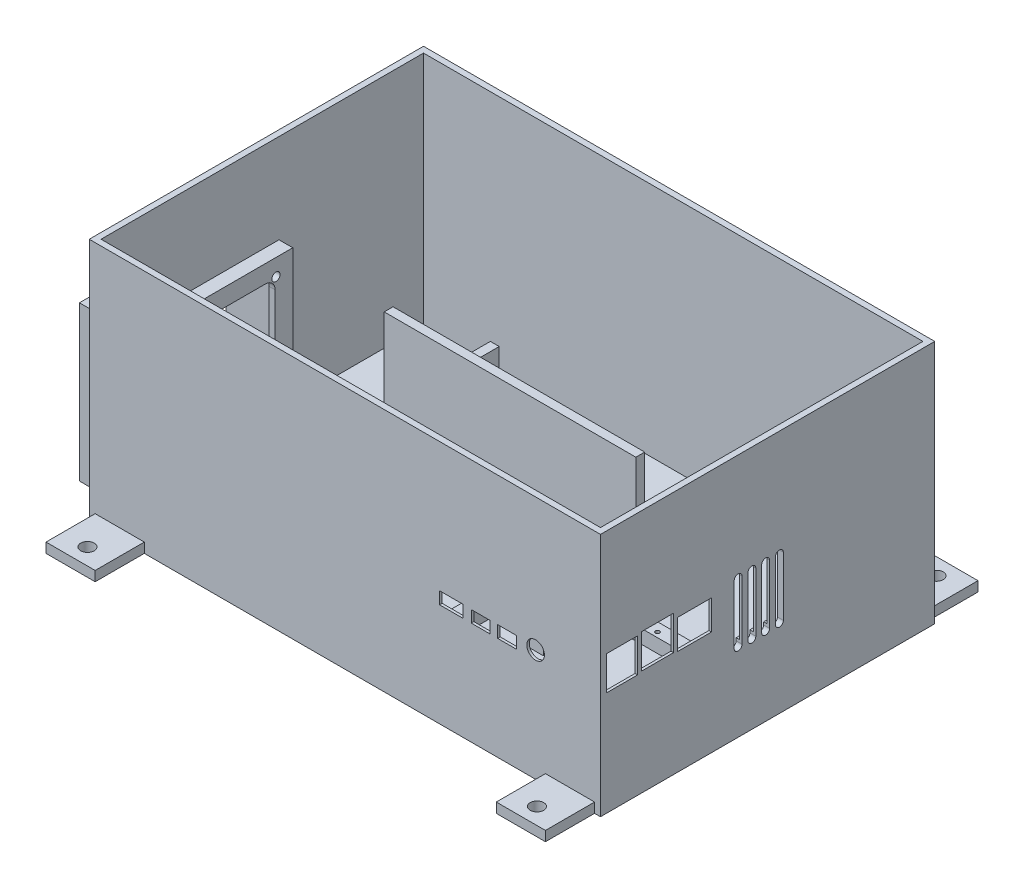
SolidWorks part; units mm, degrees
ref_plane "Front Plane" through (0, 0, 0) normal (0, 0, 1) x (1, 0, 0)
ref_plane "Top Plane" through (0, 0, 0) normal (0, 1, 0) x (1, 0, 0)
ref_plane "Right Plane" through (0, 0, 0) normal (1, 0, 0) x (0, 0, -1)
sketch "Sketch1" plane through (0, 0, 0) normal (0, 1, 0) x (1, 0, 0)
  line L1 (-130, -85) -> (130, -85)
  line L2 (-130, -85) -> (-130, 85)
  line L3 (-130, 85) -> (130, 85)
  line L4 (130, -85) -> (130, 85)
  line L5 (-130, -85) -> (130, 85) construction
  line L6 (-130, 85) -> (130, -85) construction
  point P0 (0, 0)
  dimension "D1" = 170
  dimension "D2" = 260
extrude "Floor" add sketch "Sketch1" along normal blind 4.3805
sketch "Sketch2" plane through (0, 4.3805, 0) normal (0, 1, 0) x (1, 0, 0)
  line L0 (127, -82) -> (127, 82)
  line L1 (127, 82) -> (-127, 82)
  line L2 (-127, 82) -> (-127, -82)
  line L3 (-127, -82) -> (127, -82)
  line L4 (130, -85) -> (130, 85)
  line L5 (130, 85) -> (-130, 85)
  line L6 (-130, 85) -> (-130, -85)
  line L7 (-130, -85) -> (130, -85)
  line L8 (130, -85) -> (130, 85)
  line L9 (130, 85) -> (-130, 85)
  line L10 (-130, 85) -> (-130, -85)
  line L11 (-130, -85) -> (130, -85)
  dimension "D1" = 0
  dimension "D2" = 3
extrude "Wall" add sketch "Sketch2" along normal blind 120
sketch "Sketch4" plane through (0, 4.3805, 0) normal (0, 1, 0) x (1, 0, 0)
  line L0 (120, -33) -> (49, -33)
  line L1 (127, -82) -> (42, -82)
  line L2 (127, -82) -> (127, -26)
  line L3 (127, -26) -> (42, -26)
  line L4 (42, -82) -> (42, -26)
  line L5 (49, -75) -> (49, -33)
  line L6 (120, -75) -> (49, -75)
  line L7 (120, -75) -> (120, -33)
  dimension "D1" = 85
  dimension "D2" = 56
  dimension "D3" = 7
extrude "Rpi stand" add sketch "Sketch4" along normal blind 7 from offset 30
sketch "Sketch7" plane through (0, 124.3805, 0) normal (0, 1, 0) x (1, 0, 0)
  point P11 (-127, -82)
  point P19 (-126.474, -85)
  point P20 (-130, 85)
sketch "Sketch3" plane through (0, 0, 0) normal (0, 1, 0) x (1, 0, 0)
  line L0 (-114.3, 101.6) -> (114.3, 101.6) construction
  line L1 (-127, 85) -> (-102, 85)
  line L2 (-127, 85) -> (-127, 110)
  line L3 (-127, 110) -> (-102, 110)
  line L4 (-102, 85) -> (-102, 110)
  line L5 (127, 85) -> (102, 85)
  line L6 (127, 85) -> (127, 110)
  line L7 (127, 110) -> (102, 110)
  line L8 (102, 85) -> (102, 110)
  line L9 (-127, -85) -> (-102, -85)
  line L10 (-127, -85) -> (-127, -110)
  line L11 (-127, -110) -> (-102, -110)
  line L12 (-102, -85) -> (-102, -110)
  line L13 (127, -85) -> (102, -85)
  line L14 (127, -85) -> (127, -110)
  line L15 (127, -110) -> (102, -110)
  line L16 (102, -85) -> (102, -110)
  line L17 (114.3, 101.6) -> (114.3, -101.6) construction
  line L18 (114.3, -101.6) -> (-114.3, -101.6) construction
  line L19 (-114.3, -101.6) -> (-114.3, 101.6) construction
  line L20 (-130, 0) -> (130, 0) construction
  line L21 (130, 85) -> (-130, 85) construction
  line L22 (130, -85) -> (130, 85) construction
  line L23 (0, 101.6) -> (0, -101.6) construction
  line L26 (-130, 85) -> (-130, -85) construction
  line L27 (-130, -85) -> (130, -85) construction
  circle A0 centre (-114.3, 101.6) radius 3.429
  circle A1 centre (114.3, 101.6) radius 3.429
  circle A2 centre (114.3, -101.6) radius 3.429
  circle A3 centre (-114.3, -101.6) radius 3.429
  point P4 (-130, -85)
  point P9 (130, -85)
  point P28 (-114.5, -85)
  point P29 (-102, -97.5)
  point P30 (114.5, -85)
  point P31 (-102, 97.5)
  dimension "D5" = 6.858
  dimension "D1" = 25
  dimension "D2" = 25
  dimension "D3" = 25
  dimension "D6" = 203.2
  dimension "D7" = 228.6
  dimension "D8" = 3
  dimension "D9" = 3
  dimension "D4" = 25
extrude "Brackets" add sketch "Sketch3" along normal blind 5
sketch "Sketch5" plane through (-130, 0, 0) normal (-1, 0, 0) x (0, 0, 1)
  line L0 (-8.5, 78.8805) -> (70, 78.8805)
  line L1 (-1, 4.3805) -> (62.5, 4.3805)
  line L2 (-4.5, 7.8805) -> (-4.5, 71.3805)
  line L3 (-1, 74.8805) -> (62.5, 74.8805)
  line L4 (66, 7.8805) -> (66, 71.3805)
  line L5 (70, 0.3805) -> (70, 78.8805)
  line L6 (-8.5, 0.3805) -> (70, 0.3805)
  line L7 (-8.5, 0.3805) -> (-8.5, 78.8805)
  line L8 (-4.5, 4.3805) -> (66, 4.3805) construction
  line L9 (110, 5) -> (110, 0) construction
  line L10 (-4.5, 4.3805) -> (-4.5, 74.8805) construction
  line L11 (-82, 4.3805) -> (82, 4.3805) construction
  line L12 (66, 4.3805) -> (66, 74.8805) construction
  line L13 (-4.5, 74.8805) -> (66, 74.8805) construction
  arc A0 (-1, 4.3805) -> (-4.5, 7.8805) centre (-1, 7.8805) cw
  arc A1 (62.5, 4.3805) -> (66, 7.8805) centre (62.5, 7.8805) ccw
  arc A2 (62.5, 74.8805) -> (66, 71.3805) centre (62.5, 71.3805) cw
  arc A3 (-4.5, 71.3805) -> (-1, 74.8805) centre (-1, 71.3805) cw
  dimension "D4" = 3.5
  dimension "D1" = 70.5
  dimension "D2" = 70.5
  dimension "D5" = 40
  dimension "D3" = 4
extrude "Fan Holder" add sketch "Sketch5" along normal blind 20 and the other way blind 10
sketch "Sketch8" plane through (-130, 0, 0) normal (-1, 0, 0) x (0, 0, 1)
  line L4 (-4.5, 71.3805) -> (-4.5, 7.8805)
  line L5 (-1, 4.3805) -> (62.5, 4.3805)
  line L6 (66, 7.8805) -> (66, 71.3805)
  line L7 (62.5, 74.8805) -> (-1, 74.8805)
  line L8 (-4.5, 71.3805) -> (-4.5, 7.8805)
  line L9 (-1, 4.3805) -> (62.5, 4.3805)
  line L10 (66, 7.8805) -> (66, 71.3805)
  line L23 (62.5, 74.8805) -> (-1, 74.8805)
  arc A2 (-4.5, 7.8805) -> (-1, 4.3805) centre (-1, 7.8805) ccw
  arc A3 (-4.5, 7.8805) -> (-1, 4.3805) centre (-1, 7.8805) ccw
  arc A4 (62.5, 4.3805) -> (66, 7.8805) centre (62.5, 7.8805) ccw
  arc A5 (62.5, 4.3805) -> (66, 7.8805) centre (62.5, 7.8805) ccw
  arc A8 (66, 71.3805) -> (62.5, 74.8805) centre (62.5, 71.3805) ccw
  arc A14 (66, 71.3805) -> (62.5, 74.8805) centre (62.5, 71.3805) ccw
  arc A16 (-1, 74.8805) -> (-4.5, 71.3805) centre (-1, 71.3805) ccw
  arc A17 (-1, 74.8805) -> (-4.5, 71.3805) centre (-1, 71.3805) ccw
  dimension "D1" = 0
extrude "Fan hole" cut sketch "Sketch8" against normal up to next
sketch "Sketch11" plane through (-120, 0, 0) normal (-1, 0, 0) x (0, 0, 1)
  line L0 (-8.5, 39.6305) -> (70, 39.6305) construction
  line L1 (30.75, 78.8805) -> (30.75, 0.3805) construction
  line L3 (0.05, 8.9305) -> (61.45, 8.9305) construction
  line L4 (-8.5, 78.8805) -> (-8.5, 0.3805)
  line L5 (-8.5, 0.3805) -> (70, 0.3805)
  line L6 (70, 0.3805) -> (70, 78.8805)
  line L7 (70, 78.8805) -> (-8.5, 78.8805)
  line L8 (-8.5, 78.8805) -> (-8.5, 0.3805)
  line L9 (-8.5, 0.3805) -> (70, 0.3805)
  line L10 (70, 0.3805) -> (70, 78.8805)
  line L11 (70, 78.8805) -> (-8.5, 78.8805)
  line L12 (0.05, 8.9305) -> (0.05, 70.3305) construction
  line L13 (0.05, 70.3305) -> (61.45, 70.3305) construction
  line L14 (61.45, 8.9305) -> (61.45, 70.3305) construction
  line L15 (0.05, 8.9305) -> (61.45, 70.3305) construction
  line L16 (0.5, 69.8805) -> (0.5, 9.3805)
  line L17 (0.5, 9.3805) -> (61, 9.3805)
  line L18 (61, 9.3805) -> (61, 69.8805)
  line L19 (61, 69.8805) -> (0.5, 69.8805)
  line L20 (0.5, 64.8805) -> (0.5, 14.3805)
  line L21 (5.5, 9.3805) -> (56, 9.3805)
  line L22 (61, 14.3805) -> (61, 64.8805)
  line L23 (56, 69.8805) -> (5.5, 69.8805)
  line L24 (0.05, 70.3305) -> (61.45, 8.9305) construction
  arc A0 (0.5, 14.3805) -> (5.5, 9.3805) centre (5.5, 14.3805) ccw
  arc A1 (56, 9.3805) -> (61, 14.3805) centre (56, 14.3805) ccw
  arc A2 (61, 64.8805) -> (56, 69.8805) centre (56, 64.8805) ccw
  arc A3 (0.5, 64.8805) -> (5.5, 69.8805) centre (5.5, 64.8805) cw
  circle A4 centre (0.05, 70.3305) radius 2.1
  circle A5 centre (61.45, 70.3305) radius 2.1
  circle A6 centre (61.45, 8.9305) radius 2.1
  circle A7 centre (0.05, 8.9305) radius 2.1
  point P24 (30.75, 39.6305)
  point P34 (30.75, 39.6305)
  dimension "D3" = 5
  dimension "D6" = 4.2
  dimension "D4" = 61.4
  dimension "D5" = 61.4
  dimension "D1" = 0
  dimension "D2" = 9
extrude "Boss-Extrude9" add sketch "Sketch11" along normal blind 3
sketch "Sketch12" plane through (0, 34.3805, 0) normal (0, -1, 0) x (1, 0, 0)
  line L1 (42, 26) -> (49, 26)
  line L2 (42, 26) -> (42, 33)
  line L3 (42, 33) -> (49, 33)
  line L4 (49, 26) -> (49, 33)
  dimension "D1" = 7
  dimension "D2" = 7
extrude "Boss-Extrude10" add sketch "Sketch12" along normal up to next
sketch "Sketch13" plane through (0, 4.3805, 0) normal (0, 1, 0) x (1, 0, 0)
  line L0 (127, 82) -> (-127, 82) construction
  line L2 (-107, -57) -> (-107, 5.7) construction
  line L3 (-107, 5.7) -> (-69.4, 5.7) construction
  line L4 (-107, -57) -> (-69.4, -57) construction
  line L5 (-69.4, 5.7) -> (-69.4, -57) construction
  line L6 (-69.4, 5.7) -> (-57.4, 5.7) construction
  line L7 (-57.4, 5.7) -> (-57.4, -57) construction
  line L8 (-57.4, -57) -> (-19.8, -57) construction
  line L9 (-19.8, -57) -> (-19.8, 5.7) construction
  line L10 (-19.8, 5.7) -> (-57.4, 5.7) construction
  line L11 (-69.4, -57) -> (-57.4, -57) construction
  line L12 (-19.8, -57) -> (62.83, -57) construction
  line L13 (62.83, -57) -> (62.83, -25.4) construction
  line L14 (62.83, -25.4) -> (105, -25.4) construction
  line L15 (105, -25.4) -> (105, -57) construction
  line L16 (105, -57) -> (62.83, -57) construction
  line L17 (118, 82) -> (118, 21.5) construction
  line L18 (-16.3, -57.85) -> (-16.3, 6.55) construction
  line L20 (127, -82) -> (127, 82) construction
  line L21 (118, 21.5) -> (120.7, 21.5) construction
  line L22 (118, 21.5) -> (41.5, 21.5) construction
  line L23 (-6.3, -47) -> (30.69, -47) construction
  line L24 (-6.3, -47) -> (-6.3, -6.4) construction
  line L25 (-6.3, -6.4) -> (30.69, -6.4) construction
  line L26 (30.69, -47) -> (30.69, -6.4) construction
  line L27 (-6.3, -47) -> (30.69, -6.4) construction
  line L28 (-6.3, -6.4) -> (30.69, -47) construction
  line L29 (130, -85) -> (130, 85) construction
  line L30 (-127, -82) -> (127, -82) construction
  line L457 (-127, 8.5) -> (-127, -70) construction
  line L458 (-127, -82) -> (127, -82) construction
  circle A0 centre (-107, -57) radius 1.25
  circle A1 centre (-107, 5.7) radius 1.25
  circle A2 centre (-69.4, 5.7) radius 1.25
  circle A3 centre (-69.4, -57) radius 1.25
  circle A4 centre (-57.4, 5.7) radius 1.25
  circle A5 centre (-57.4, -57) radius 1.25
  circle A6 centre (-19.8, -57) radius 1.25
  circle A7 centre (-19.8, 5.7) radius 1.25
  circle A12 centre (120.7, 21.5) radius 1.25
  circle A13 centre (41.5, 21.5) radius 1.25
  circle A14 centre (-107, 5.7) radius 2.75
  circle A15 centre (-107, -57) radius 2.75
  circle A16 centre (-69.4, 5.7) radius 2.75
  circle A17 centre (-57.4, 5.7) radius 2.75
  circle A18 centre (-69.4, -57) radius 2.75
  circle A19 centre (-57.4, -57) radius 2.75
  circle A20 centre (-19.8, -57) radius 2.75
  circle A21 centre (-19.8, 5.7) radius 2.75
  circle A22 centre (62.83, -57) radius 2.5
  circle A23 centre (62.83, -25.4) radius 2.5
  circle A24 centre (105, -25.4) radius 2.5
  circle A25 centre (105, -57) radius 2.5
  circle A26 centre (-6.3, -47) radius 1.25
  circle A28 centre (-6.3, -47) radius 2.75
  circle A30 centre (-69.4, 5.7) radius 1.65 construction
  circle A31 centre (104.2333, -41.2) radius 1.5 construction
  circle A32 centre (104.2333, -41.2) radius 1.5 construction
  circle A33 centre (63.5933, -41.2) radius 1.5 construction
  circle A34 centre (63.5933, -41.2) radius 1.5 construction
  circle A35 centre (104.2333, -41.2) radius 3
  circle A36 centre (63.5933, -41.2) radius 3
  circle A37 centre (-6.3, -6.4) radius 1.25
  circle A38 centre (30.69, -6.4) radius 1.25
  circle A39 centre (30.69, -47) radius 1.25
  circle A40 centre (-6.3, -6.4) radius 2.75
  circle A41 centre (30.69, -6.4) radius 2.75
  circle A42 centre (30.69, -47) radius 2.75
  circle A43 centre (30.69, -6.4) radius 1.5 construction
  circle A44 centre (30.69, -6.4) radius 1.5 construction
  point P2 (-127, -82)
  point P3 (127, -82)
  point P8 (12.195, -26.7)
  point P31 (127, 82)
  point P32 (-127, 82)
  point P90 (-123, -62.5)
  point P91 (-123, -66)
  point P92 (-130, -70)
  point P93 (-130, 8.5)
  point P94 (-127, 8.5)
  point P95 (-127, -70)
  point P96 (-127, 8.5)
  point P97 (-120, 8.5)
  point P98 (-120, -70)
  point P99 (-127, -70)
  point P100 (-120, 8.5)
  point P101 (-120, -70)
  point P102 (-130, -85)
  point P103 (-127, -85)
  point P104 (-102, -85)
  point P105 (102, -85)
  point P106 (127, -85)
  point P107 (130, -85)
  point P108 (-130, 85)
  point P109 (-130, -85)
  point P110 (130, 85)
  point P111 (127, 85)
  point P112 (102, 85)
  point P113 (-102, 85)
  point P114 (-127, 85)
  point P115 (-130, 85)
  point P116 (130, -85)
  point P117 (130, 85)
  point P118 (-130, 85)
  point P119 (-130, -85)
  point P120 (130, 85)
  point P121 (-130, 85)
  point P122 (130, -85)
  point P123 (130, 85)
  point P124 (-130, -85)
  point P125 (130, -85)
  point P126 (-127, 82)
  point P127 (-127, -82)
  point P128 (127, 82)
  point P129 (-127, 82)
  point P130 (127, -82)
  point P131 (127, 82)
  point P132 (-127, -82)
  point P133 (127, -82)
  point P134 (-127, 82)
  point P135 (-127, 8.5)
  point P136 (-127, -70)
  point P137 (-127, -82)
  point P138 (127, -82)
  point P139 (127, 82)
  point P140 (42, -82)
  point P141 (127, -82)
  point P142 (42, -26)
  point P143 (42, -82)
  point P144 (127, -26)
  point P145 (42, -26)
  point P146 (127, -82)
  point P147 (127, -26)
  point P148 (42, -82)
  point P149 (127, -82)
  point P150 (42, -33)
  point P151 (42, -82)
  point P152 (127, -26)
  point P153 (49, -26)
  point P154 (127, -82)
  point P155 (127, -26)
  point P156 (49, -75)
  point P157 (120, -75)
  point P158 (49, -33)
  point P159 (49, -75)
  point P160 (120, -33)
  point P161 (49, -33)
  point P162 (120, -75)
  point P163 (120, -33)
  point P164 (49, -75)
  point P165 (120, -75)
  point P166 (49, -33)
  point P167 (49, -75)
  point P168 (120, -33)
  point P169 (49, -33)
  point P170 (120, -75)
  point P171 (120, -33)
  point P172 (-102, 110)
  point P173 (-127, 110)
  point P174 (-102, 85)
  point P175 (-102, 110)
  point P176 (-127, 85)
  point P177 (-102, 85)
  point P178 (-127, 110)
  point P179 (-127, 85)
  point P180 (-102, 110)
  point P181 (-127, 110)
  point P182 (-102, 85)
  point P183 (-102, 110)
  point P184 (-127, 110)
  point P185 (-127, 85)
  point P186 (-114.3, 101.6)
  point P187 (-111.0208, 102.6025)
  point P188 (-114.3, 101.6)
  point P189 (-111.0208, 102.6025)
  point P190 (114.3, 101.6)
  point P191 (117.5792, 102.6025)
  point P192 (114.3, 101.6)
  point P193 (117.5792, 102.6025)
  point P194 (127, 85)
  point P195 (127, 110)
  point P196 (127, 110)
  point P197 (102, 110)
  point P198 (102, 110)
  point P199 (102, 85)
  point P200 (127, 85)
  point P201 (127, 110)
  point P202 (127, 110)
  point P203 (102, 110)
  point P204 (102, 110)
  point P205 (102, 85)
  point P206 (102, 85)
  point P207 (127, 85)
  point P208 (-114.3, -101.6)
  point P209 (-111.0208, -100.5975)
  point P210 (-114.3, -101.6)
  point P211 (-111.0208, -100.5975)
  point P212 (-127, -85)
  point P213 (-127, -110)
  point P214 (-127, -110)
  point P215 (-102, -110)
  point P216 (-102, -110)
  point P217 (-102, -85)
  point P218 (-127, -85)
  point P219 (-127, -110)
  point P220 (-127, -110)
  point P221 (-102, -110)
  point P222 (-102, -110)
  point P223 (-102, -85)
  point P224 (-102, -85)
  point P225 (-127, -85)
  point P226 (114.3, -101.6)
  point P227 (117.5792, -100.5975)
  point P228 (114.3, -101.6)
  point P229 (117.5792, -100.5975)
  point P230 (127, -110)
  point P231 (127, -85)
  point P232 (102, -85)
  point P233 (102, -110)
  point P234 (102, -110)
  point P235 (127, -110)
  point P236 (127, -110)
  point P237 (127, -85)
  point P238 (127, -85)
  point P239 (102, -85)
  point P240 (102, -85)
  point P241 (102, -110)
  point P242 (102, -110)
  point P243 (127, -110)
  point P244 (-130, 8.5)
  point P245 (-130, -70)
  point P246 (-120, 8.5)
  point P247 (-127, 8.5)
  point P248 (-130, 8.5)
  point P249 (-150, 8.5)
  point P250 (-120, -70)
  point P251 (-127, -70)
  point P252 (-130, -70)
  point P253 (-150, -70)
  point P254 (-130, -70)
  point P255 (-150, -70)
  point P256 (-130, 8.5)
  point P257 (-150, 8.5)
  point P258 (-120, -70)
  point P259 (-120, 8.5)
  point P260 (-123, 4.5)
  point P261 (-150, 4.5)
  point P262 (-123, 4.5)
  point P263 (-150, 4.5)
  point P264 (-123, 1)
  point P265 (-150, 1)
  point P266 (-123, -62.5)
  point P267 (-150, -62.5)
  point P268 (-123, -66)
  point P269 (-150, -66)
  point P270 (-123, -66)
  point P271 (-150, -66)
  point P272 (-123, -62.5)
  point P273 (-150, -62.5)
  point P274 (-123, 1)
  point P275 (-150, 1)
  point P276 (-150, -70)
  point P277 (-150, 8.5)
  point P278 (-150, 8.5)
  point P279 (-150, -70)
  point P280 (-150, 4.5)
  point P281 (-150, 1)
  point P282 (-150, -62.5)
  point P283 (-150, 1)
  point P284 (-150, -62.5)
  point P285 (-150, -66)
  point P286 (-150, -62.5)
  point P287 (-150, -66)
  point P288 (-150, 1)
  point P289 (-150, -62.5)
  point P290 (-150, 4.5)
  point P291 (-150, 1)
  point P292 (-123, 4.5)
  point P293 (-123, 1)
  point P294 (-123, -62.5)
  point P295 (-123, 1)
  point P296 (-123, 4.5)
  point P297 (-123, 1)
  point P298 (-123, 1)
  point P299 (-123, -62.5)
  point P300 (-123, -62.5)
  point P301 (-123, -66)
  point P302 (-123, -5.5)
  point P303 (-120, -5.5)
  point P304 (-123, -56)
  point P305 (-120, -56)
  point P306 (-123, -61)
  point P307 (-120, -61)
  point P308 (-123, -61)
  point P309 (-120, -61)
  point P310 (-123, -56)
  point P311 (-120, -56)
  point P312 (-123, -5.5)
  point P313 (-120, -5.5)
  point P314 (-123, -0.5)
  point P315 (-120, -0.5)
  point P316 (-123, -0.5)
  point P317 (-120, -0.5)
  point P318 (-123, -0.5)
  point P319 (-123, -5.5)
  point P320 (-123, -56)
  point P321 (-123, -5.5)
  point P322 (-123, -56)
  point P323 (-123, -61)
  point P324 (-123, -56)
  point P325 (-123, -61)
  point P326 (-123, -5.5)
  point P327 (-123, -56)
  point P328 (-123, -0.5)
  point P329 (-123, -5.5)
  point P330 (-120, -5.5)
  point P331 (-120, -0.5)
  point P332 (-120, -56)
  point P333 (-120, -5.5)
  point P334 (-120, -61)
  point P335 (-120, -56)
  point P336 (-120, -61)
  point P337 (-120, -56)
  point P338 (-120, -5.5)
  point P339 (-120, -56)
  point P340 (-120, -5.5)
  point P341 (-120, -0.5)
  point P342 (-123, 2.05)
  point P343 (-123, -2.15)
  point P344 (-120, -2.15)
  point P345 (-120, 2.05)
  point P346 (-123, -59.35)
  point P347 (-123, -63.55)
  point P348 (-120, -63.55)
  point P349 (-120, -59.35)
  point P350 (-123, -59.35)
  point P351 (-123, -63.55)
  point P352 (-120, -63.55)
  point P353 (-120, -59.35)
  point P354 (-123, 2.05)
  point P355 (-123, -2.15)
  point P356 (-120, -2.15)
  point P357 (-120, 2.05)
  point P358 (49, -33)
  point P359 (42, -33)
  point P360 (49, -26)
  point P361 (49, -33)
  point P362 (42, -33)
  point P363 (42, -26)
  point P364 (42, -26)
  point P365 (49, -26)
  point P366 (49, -26)
  point P367 (49, -33)
  point P368 (49, -33)
  point P369 (42, -33)
  point P370 (-130, -85)
  point P371 (130, -85)
  point P372 (-130, -85)
  point P373 (-130, 85)
  point P374 (-130, 85)
  point P375 (130, 85)
  point P376 (130, -85)
  point P377 (130, 85)
  point P378 (-130, -85)
  point P379 (130, 85)
  point P380 (-130, 85)
  point P381 (130, -85)
  point P382 (127, -82)
  point P383 (127, 82)
  point P384 (127, 82)
  point P385 (-127, 82)
  point P386 (-127, 82)
  point P387 (-127, -82)
  point P388 (-127, -82)
  point P389 (127, -82)
  point P390 (130, -85)
  point P391 (130, 85)
  point P392 (130, 85)
  point P393 (-130, 85)
  point P394 (-130, 85)
  point P395 (-130, -85)
  point P396 (-130, -85)
  point P397 (130, -85)
  point P398 (130, -85)
  point P399 (130, 85)
  point P400 (130, 85)
  point P401 (-130, 85)
  point P402 (-130, 85)
  point P403 (-130, -85)
  point P404 (-130, -85)
  point P405 (130, -85)
  point P406 (120, -33)
  point P407 (49, -33)
  point P408 (127, -82)
  point P409 (42, -82)
  point P410 (127, -82)
  point P411 (127, -26)
  point P412 (127, -26)
  point P413 (42, -26)
  point P414 (42, -82)
  point P415 (42, -26)
  point P416 (49, -75)
  point P417 (49, -33)
  point P418 (120, -75)
  point P419 (49, -75)
  point P420 (120, -75)
  point P421 (120, -33)
  point P422 (-114.3, 101.6)
  point P423 (114.3, 101.6)
  point P424 (-127, 85)
  point P425 (-102, 85)
  point P426 (-127, 85)
  point P427 (-127, 110)
  point P428 (-127, 110)
  point P429 (-102, 110)
  point P430 (-102, 85)
  point P431 (-102, 110)
  point P432 (127, 85)
  point P433 (102, 85)
  point P434 (127, 85)
  point P435 (127, 110)
  point P436 (127, 110)
  point P437 (102, 110)
  point P438 (102, 85)
  point P439 (102, 110)
  point P440 (-127, -85)
  point P441 (-102, -85)
  point P442 (-127, -85)
  point P443 (-127, -110)
  point P444 (-127, -110)
  point P445 (-102, -110)
  point P446 (-102, -85)
  point P447 (-102, -110)
  point P448 (127, -85)
  point P449 (102, -85)
  point P450 (127, -85)
  point P451 (127, -110)
  point P452 (127, -110)
  point P453 (102, -110)
  point P454 (102, -85)
  point P455 (102, -110)
  point P456 (114.3, 101.6)
  point P457 (114.3, -101.6)
  point P458 (114.3, -101.6)
  point P459 (-114.3, -101.6)
  point P460 (-114.3, -101.6)
  point P461 (-114.3, 101.6)
  point P462 (-130, 0)
  point P463 (130, 0)
  point P464 (130, 85)
  point P465 (-130, 85)
  point P466 (130, -85)
  point P467 (130, 85)
  point P468 (0, 101.6)
  point P469 (0, -101.6)
  point P470 (-130, 85)
  point P471 (-130, -85)
  point P472 (-130, -85)
  point P473 (130, -85)
  point P474 (-130, 8.5)
  point P475 (-130, -70)
  point P476 (-130, 1)
  point P477 (-130, -62.5)
  point P478 (-130, 1)
  point P479 (-130, -62.5)
  point P480 (-130, 8.5)
  point P481 (-130, -70)
  point P482 (-130, 4.5)
  point P483 (-130, -66)
  point P484 (-130, 82)
  point P485 (-130, -82)
  point P486 (-130, 4.5)
  point P487 (-130, -66)
  point P488 (-130, 1)
  point P489 (-130, -62.5)
  point P490 (-130, -62.5)
  point P491 (-130, 1)
  point P492 (-130, 1)
  point P493 (-130, -62.5)
  point P494 (-130, -62.5)
  point P495 (-130, 1)
  point P496 (-120, 8.5)
  point P497 (-120, -70)
  point P498 (-120, -0.05)
  point P499 (-120, -61.45)
  point P500 (-120, 8.5)
  point P501 (-120, -70)
  point P502 (-120, -70)
  point P503 (-120, 8.5)
  point P504 (-120, 8.5)
  point P505 (-120, -70)
  point P506 (-120, -70)
  point P507 (-120, 8.5)
  point P508 (-120, -0.05)
  point P509 (-120, -61.45)
  point P510 (-120, -0.05)
  point P511 (-120, -61.45)
  point P512 (-120, -0.5)
  point P513 (-120, -61)
  point P514 (-120, -61)
  point P515 (-120, -0.5)
  point P516 (-120, -5.5)
  point P517 (-120, -56)
  point P518 (-120, -56)
  point P519 (-120, -5.5)
  point P520 (-120, -0.05)
  point P521 (-120, -61.45)
  point P522 (42, -26)
  point P523 (49, -26)
  point P524 (42, -26)
  point P525 (42, -33)
  point P526 (42, -33)
  point P527 (49, -33)
  point P528 (49, -26)
  point P529 (49, -33)
  point P530 (-123, -62.5)
  point P531 (-123, -66)
  point P532 (-130, -70)
  point P533 (-130, 8.5)
  point P534 (-127, 8.5)
  point P535 (-127, -70)
  point P536 (-127, 8.5)
  point P537 (-120, 8.5)
  point P538 (-120, -70)
  point P539 (-127, -70)
  point P540 (-120, 8.5)
  point P541 (-120, -70)
  point P542 (-130, -85)
  point P543 (-127, -85)
  point P544 (-102, -85)
  point P545 (102, -85)
  point P546 (127, -85)
  point P547 (130, -85)
  point P548 (-130, 85)
  point P549 (-130, -85)
  point P550 (130, 85)
  point P551 (127, 85)
  point P552 (102, 85)
  point P553 (-102, 85)
  point P554 (-127, 85)
  point P555 (-130, 85)
  point P556 (130, -85)
  point P557 (130, 85)
  point P558 (-130, 85)
  point P559 (-130, -85)
  point P560 (130, 85)
  point P561 (-130, 85)
  point P562 (130, -85)
  point P563 (130, 85)
  point P564 (-130, -85)
  point P565 (130, -85)
  point P566 (-127, 82)
  point P567 (-127, -82)
  point P568 (127, 82)
  point P569 (-127, 82)
  point P570 (127, -82)
  point P571 (127, 82)
  point P572 (-127, -82)
  point P573 (127, -82)
  point P574 (-127, 82)
  point P575 (-127, 8.5)
  point P576 (-127, -70)
  point P577 (-127, -82)
  point P578 (127, 82)
  point P579 (-127, 82)
  point P580 (127, -82)
  point P581 (127, 82)
  point P582 (-127, -82)
  point P583 (127, -82)
  point P584 (42, -82)
  point P585 (127, -82)
  point P586 (42, -26)
  point P587 (42, -82)
  point P588 (127, -26)
  point P589 (42, -26)
  point P590 (127, -82)
  point P591 (127, -26)
  point P592 (42, -82)
  point P593 (127, -82)
  point P594 (42, -33)
  point P595 (42, -82)
  point P596 (127, -26)
  point P597 (49, -26)
  point P598 (127, -82)
  point P599 (127, -26)
  point P600 (49, -75)
  point P601 (120, -75)
  point P602 (49, -33)
  point P603 (49, -75)
  point P604 (120, -33)
  point P605 (49, -33)
  point P606 (120, -75)
  point P607 (120, -33)
  point P608 (49, -75)
  point P609 (120, -75)
  point P610 (49, -33)
  point P611 (49, -75)
  point P612 (120, -33)
  point P613 (49, -33)
  point P614 (120, -75)
  point P615 (120, -33)
  point P616 (-102, 110)
  point P617 (-127, 110)
  point P618 (-102, 85)
  point P619 (-102, 110)
  point P620 (-127, 85)
  point P621 (-102, 85)
  point P622 (-127, 110)
  point P623 (-127, 85)
  point P624 (-102, 110)
  point P625 (-127, 110)
  point P626 (-102, 85)
  point P627 (-102, 110)
  point P628 (-127, 110)
  point P629 (-127, 85)
  point P630 (-114.3, 101.6)
  point P631 (-111.0208, 102.6025)
  point P632 (-114.3, 101.6)
  point P633 (-111.0208, 102.6025)
  point P634 (114.3, 101.6)
  point P635 (117.5792, 102.6025)
  point P636 (114.3, 101.6)
  point P637 (117.5792, 102.6025)
  point P638 (127, 85)
  point P639 (127, 110)
  point P640 (127, 110)
  point P641 (102, 110)
  point P642 (102, 110)
  point P643 (102, 85)
  point P644 (127, 85)
  point P645 (127, 110)
  point P646 (127, 110)
  point P647 (102, 110)
  point P648 (102, 110)
  point P649 (102, 85)
  point P650 (102, 85)
  point P651 (127, 85)
  point P652 (-114.3, -101.6)
  point P653 (-111.0208, -100.5975)
  point P654 (-114.3, -101.6)
  point P655 (-111.0208, -100.5975)
  point P656 (-127, -85)
  point P657 (-127, -110)
  point P658 (-127, -110)
  point P659 (-102, -110)
  point P660 (-102, -110)
  point P661 (-102, -85)
  point P662 (-127, -85)
  point P663 (-127, -110)
  point P664 (-127, -110)
  point P665 (-102, -110)
  point P666 (-102, -110)
  point P667 (-102, -85)
  point P668 (-102, -85)
  point P669 (-127, -85)
  point P670 (114.3, -101.6)
  point P671 (117.5792, -100.5975)
  point P672 (114.3, -101.6)
  point P673 (117.5792, -100.5975)
  point P674 (127, -110)
  point P675 (127, -85)
  point P676 (102, -85)
  point P677 (102, -110)
  point P678 (102, -110)
  point P679 (127, -110)
  point P680 (127, -110)
  point P681 (127, -85)
  point P682 (127, -85)
  point P683 (102, -85)
  point P684 (102, -85)
  point P685 (102, -110)
  point P686 (102, -110)
  point P687 (127, -110)
  point P688 (-130, 8.5)
  point P689 (-130, -70)
  point P690 (-120, 8.5)
  point P691 (-127, 8.5)
  point P692 (-130, 8.5)
  point P693 (-150, 8.5)
  point P694 (-120, -70)
  point P695 (-127, -70)
  point P696 (-130, -70)
  point P697 (-150, -70)
  point P698 (-130, -70)
  point P699 (-150, -70)
  point P700 (-130, 8.5)
  point P701 (-150, 8.5)
  point P702 (-120, -70)
  point P703 (-120, 8.5)
  point P704 (-123, 4.5)
  point P705 (-150, 4.5)
  point P706 (-123, 4.5)
  point P707 (-150, 4.5)
  point P708 (-123, 1)
  point P709 (-150, 1)
  point P710 (-123, -62.5)
  point P711 (-150, -62.5)
  point P712 (-123, -66)
  point P713 (-150, -66)
  point P714 (-123, -66)
  point P715 (-150, -66)
  point P716 (-123, -62.5)
  point P717 (-150, -62.5)
  point P718 (-123, 1)
  point P719 (-150, 1)
  point P720 (-150, -70)
  point P721 (-150, 8.5)
  point P722 (-150, 8.5)
  point P723 (-150, -70)
  point P724 (-150, 4.5)
  point P725 (-150, 1)
  point P726 (-150, -62.5)
  point P727 (-150, 1)
  point P728 (-150, -62.5)
  point P729 (-150, -66)
  point P730 (-150, -62.5)
  point P731 (-150, -66)
  point P732 (-150, 1)
  point P733 (-150, -62.5)
  point P734 (-150, 4.5)
  point P735 (-150, 1)
  point P736 (-123, 4.5)
  point P737 (-123, 1)
  point P738 (-123, -62.5)
  point P739 (-123, 1)
  point P740 (-123, 4.5)
  point P741 (-123, 1)
  point P742 (-123, 1)
  point P743 (-123, -62.5)
  point P744 (-123, -62.5)
  point P745 (-123, -66)
  point P746 (-123, -5.5)
  point P747 (-120, -5.5)
  point P748 (-123, -56)
  point P749 (-120, -56)
  point P750 (-123, -61)
  point P751 (-120, -61)
  point P752 (-123, -61)
  point P753 (-120, -61)
  point P754 (-123, -56)
  point P755 (-120, -56)
  point P756 (-123, -5.5)
  point P757 (-120, -5.5)
  point P758 (-123, -0.5)
  point P759 (-120, -0.5)
  point P760 (-123, -0.5)
  point P761 (-120, -0.5)
  point P762 (-123, -0.5)
  point P763 (-123, -5.5)
  point P764 (-123, -56)
  point P765 (-123, -5.5)
  point P766 (-123, -56)
  point P767 (-123, -61)
  point P768 (-123, -56)
  point P769 (-123, -61)
  point P770 (-123, -5.5)
  point P771 (-123, -56)
  point P772 (-123, -0.5)
  point P773 (-123, -5.5)
  point P774 (-120, -5.5)
  point P775 (-120, -0.5)
  point P776 (-120, -56)
  point P777 (-120, -5.5)
  point P778 (-120, -61)
  point P779 (-120, -56)
  point P780 (-120, -61)
  point P781 (-120, -56)
  point P782 (-120, -5.5)
  point P783 (-120, -56)
  point P784 (-120, -5.5)
  point P785 (-120, -0.5)
  point P786 (-123, 2.05)
  point P787 (-123, -2.15)
  point P788 (-120, -2.15)
  point P789 (-120, 2.05)
  point P790 (-123, -59.35)
  point P791 (-123, -63.55)
  point P792 (-120, -63.55)
  point P793 (-120, -59.35)
  point P794 (-123, -59.35)
  point P795 (-123, -63.55)
  point P796 (-120, -63.55)
  point P797 (-120, -59.35)
  point P798 (-123, 2.05)
  point P799 (-123, -2.15)
  point P800 (-120, -2.15)
  point P801 (-120, 2.05)
  point P802 (49, -33)
  point P803 (42, -33)
  point P804 (49, -26)
  point P805 (49, -33)
  point P806 (42, -33)
  point P807 (42, -26)
  point P808 (42, -26)
  point P809 (49, -26)
  point P810 (49, -26)
  point P811 (49, -33)
  point P812 (49, -33)
  point P813 (42, -33)
  point P814 (-130, -85)
  point P815 (130, -85)
  point P816 (-130, -85)
  point P817 (-130, 85)
  point P818 (-130, 85)
  point P819 (130, 85)
  point P820 (130, -85)
  point P821 (130, 85)
  point P822 (-130, -85)
  point P823 (130, 85)
  point P824 (-130, 85)
  point P825 (130, -85)
  point P826 (127, -82)
  point P827 (127, 82)
  point P828 (127, 82)
  point P829 (-127, 82)
  point P830 (-127, 82)
  point P831 (-127, -82)
  point P832 (-127, -82)
  point P833 (127, -82)
  point P834 (130, -85)
  point P835 (130, 85)
  point P836 (130, 85)
  point P837 (-130, 85)
  point P838 (-130, 85)
  point P839 (-130, -85)
  point P840 (-130, -85)
  point P841 (130, -85)
  point P842 (130, -85)
  point P843 (130, 85)
  point P844 (130, 85)
  point P845 (-130, 85)
  point P846 (-130, 85)
  point P847 (-130, -85)
  point P848 (-130, -85)
  point P849 (130, -85)
  point P850 (120, -33)
  point P851 (49, -33)
  point P852 (127, -82)
  point P853 (42, -82)
  point P854 (127, -82)
  point P855 (127, -26)
  point P856 (127, -26)
  point P857 (42, -26)
  point P858 (42, -82)
  point P859 (42, -26)
  point P860 (49, -75)
  point P861 (49, -33)
  point P862 (120, -75)
  point P863 (49, -75)
  point P864 (120, -75)
  point P865 (120, -33)
  point P866 (-114.3, 101.6)
  point P867 (114.3, 101.6)
  point P868 (-127, 85)
  point P869 (-102, 85)
  point P870 (-127, 85)
  point P871 (-127, 110)
  point P872 (-127, 110)
  point P873 (-102, 110)
  point P874 (-102, 85)
  point P875 (-102, 110)
  point P876 (127, 85)
  point P877 (102, 85)
  point P878 (127, 85)
  point P879 (127, 110)
  point P880 (127, 110)
  point P881 (102, 110)
  point P882 (102, 85)
  point P883 (102, 110)
  point P884 (-127, -85)
  point P885 (-102, -85)
  point P886 (-127, -85)
  point P887 (-127, -110)
  point P888 (-127, -110)
  point P889 (-102, -110)
  point P890 (-102, -85)
  point P891 (-102, -110)
  point P892 (127, -85)
  point P893 (102, -85)
  point P894 (127, -85)
  point P895 (127, -110)
  point P896 (127, -110)
  point P897 (102, -110)
  point P898 (102, -85)
  point P899 (102, -110)
  point P900 (114.3, 101.6)
  point P901 (114.3, -101.6)
  point P902 (114.3, -101.6)
  point P903 (-114.3, -101.6)
  point P904 (-114.3, -101.6)
  point P905 (-114.3, 101.6)
  point P906 (-130, 0)
  point P907 (130, 0)
  point P908 (130, 85)
  point P909 (-130, 85)
  point P910 (130, -85)
  point P911 (130, 85)
  point P912 (0, 101.6)
  point P913 (0, -101.6)
  point P914 (-130, 85)
  point P915 (-130, -85)
  point P916 (-130, -85)
  point P917 (130, -85)
  point P918 (-130, 8.5)
  point P919 (-130, -70)
  point P920 (-130, 1)
  point P921 (-130, -62.5)
  point P922 (-130, 1)
  point P923 (-130, -62.5)
  point P924 (-130, 8.5)
  point P925 (-130, -70)
  point P926 (-130, 4.5)
  point P927 (-130, -66)
  point P928 (-130, 82)
  point P929 (-130, -82)
  point P930 (-130, 4.5)
  point P931 (-130, -66)
  point P932 (-130, 1)
  point P933 (-130, -62.5)
  point P934 (-130, -62.5)
  point P935 (-130, 1)
  point P936 (-130, 1)
  point P937 (-130, -62.5)
  point P938 (-130, -62.5)
  point P939 (-130, 1)
  point P940 (-120, 8.5)
  point P941 (-120, -70)
  point P942 (-120, -0.05)
  point P943 (-120, -61.45)
  point P944 (-120, 8.5)
  point P945 (-120, -70)
  point P946 (-120, -70)
  point P947 (-120, 8.5)
  point P948 (-120, 8.5)
  point P949 (-120, -70)
  point P950 (-120, -70)
  point P951 (-120, 8.5)
  point P952 (-120, -0.05)
  point P953 (-120, -61.45)
  point P954 (-120, -0.05)
  point P955 (-120, -61.45)
  point P956 (-120, -0.5)
  point P957 (-120, -61)
  point P958 (-120, -61)
  point P959 (-120, -0.5)
  point P960 (-120, -5.5)
  point P961 (-120, -56)
  point P962 (-120, -56)
  point P963 (-120, -5.5)
  point P964 (-120, -0.05)
  point P965 (-120, -61.45)
  point P966 (42, -26)
  point P967 (49, -26)
  point P968 (42, -26)
  point P969 (42, -33)
  point P970 (42, -33)
  point P971 (49, -33)
  point P972 (49, -26)
  point P973 (49, -33)
  point P975 (118, 82)
  dimension "D3" = 2.5
  dimension "D6" = 1.5
  dimension "D7" = 2.5
  dimension "D8" = 10
  dimension "D11" = 35
  dimension "D12" = 20
  dimension "D13" = 25
  dimension "D25" = 2.5
  dimension "D27" = 2.5
  dimension "D4" = 5
  dimension "D5" = 25
  dimension "D9" = 12
  dimension "D10" = 1.5
  dimension "D17" = 31.6
  dimension "D19" = 42.17
  dimension "D22" = 60.5
  dimension "D23" = 9
  dimension "D24" = 2.7
  dimension "D26" = 76.5
  dimension "D28" = 1.5
extrude "Built in Standoffs" add sketch "Sketch13" along normal blind 5 contours A1 | A16 A2 | A2 | A17 A4 | A4 | A14 A1 | A21 A7 | A7 | A15 A0 | A0 | A18 A3 | A3 | A19 A5 | A5 | A20 A6 | A6 | A22 | A23 | A24 A32 | A32 | A25 | A36 | A35 | A28 A26 | A26 | A40 A37 | A37 | A41 A38 | A38 | A42 A39 | A39 region at (-107, 4.3805, 57) region at (-107, 4.3805, -5.7) region at (-69.4, 4.3805, -5.7) region at (-69.4, 4.3805, 57) region at (-57.4, 4.3805, -5.7) region at (-57.4, 4.3805, 57) region at (-19.8, 4.3805, 57) region at (-19.8, 4.3805, -5.7) region at (-109.6722, 4.3805, -5.7) region at (-109.6722, 4.3805, 57) region at (-72.0722, 4.3805, -5.7) region at (-60.0722, 4.3805, -5.7) region at (-72.0722, 4.3805, 57) region at (-60.0722, 4.3805, 57) region at (-22.4722, 4.3805, 57) region at (-22.4722, 4.3805, -5.7) region at (62.83, 4.3805, 57) region at (62.83, 4.3805, 25.4) region at (105, 4.3805, 25.4) region at (105, 4.3805, 57) region at (-6.3, 4.3805, 47) region at (-8.9722, 4.3805, 47) region at (104.2333, 4.3805, 41.2) region at (63.5933, 4.3805, 41.2) region at (-6.3, 4.3805, 6.4) region at (30.69, 4.3805, 6.4) region at (30.69, 4.3805, 47) region at (-8.9722, 4.3805, 6.4) region at (28.0178, 4.3805, 6.4) region at (28.0178, 4.3805, 47)
sketch "Sketch19" plane through (0, 9.3805, 0) normal (0, 1, 0) x (1, 0, 0)
  circle A0 centre (104.2333, -41.2) radius 1.25
  circle A1 centre (63.5933, -41.2) radius 1.25
  dimension "D1" = 2.5
  dimension "D2" = 2.5
extrude "Bread board holes" cut sketch "Sketch19" against normal blind 7
sketch "Sketch14" plane through (0, 4.3805, 0) normal (0, 1, 0) x (1, 0, 0)
  line L0 (127, 82) -> (-88, 82)
  line L1 (127, 82) -> (-127, 82) construction
  line L2 (-88, 82) -> (-88, 32)
  line L3 (-88, 32) -> (127, 32)
  line L4 (127, -82) -> (127, 82) construction
  line L5 (127, 32) -> (127, 82)
  dimension "D1" = 215
  dimension "D2" = 50
extrude "Screw Holes" cut sketch "Sketch13<4>" against normal blind 7 from surface contours A37 | A38 | A26 | A39 | A1 | A0 | A3 | A5 | A2 | A4 | A7 | A6 | A32 region at (-6.3, 4.3805, 47) region at (-6.3, 4.3805, 6.4) region at (30.69, 4.3805, 6.4) region at (30.69, 4.3805, 47) starting at face at (-107, 9.3805, -2.95)
sketch "Sketch13<4>" plane through (0, 4.3805, 0) normal (0, 1, 0) x (1, 0, 0) same geometry as "Sketch13"
extrude "Driver Screw Holes" cut sketch "Sketch13<5>" against normal blind 3 contours A13 | A12
sketch "Sketch13<5>" plane through (0, 4.3805, 0) normal (0, 1, 0) x (1, 0, 0) same geometry as "Sketch13"
sketch "Sketch16" plane through (0, 4.3805, 0) normal (0, 1, 0) x (1, 0, 0)
  line L0 (-93, 82) -> (-93, 28)
  line L1 (-93, 28) -> (35, 28)
  line L2 (-88.5, 82) -> (-88.5, 32.5)
  line L3 (-88.5, 32.5) -> (35, 32.5)
  line L10 (-88, 82) -> (-88, 33) construction
  line L11 (-88, 33) -> (29.1074, 33) construction
  line L14 (-93, 28) -> (127, 28) construction
  line L16 (-88, 33) -> (127, 33) construction
  line L17 (-88.5, 82) -> (-93, 82)
  line L20 (35, 28) -> (35, 32.5)
  line L21 (-88.5, 32.5) -> (29.1074, 32.5) construction
  line L25 (-88, 33) -> (127, 33)
  line L26 (127, 33) -> (127, 82)
  line L27 (127, 82) -> (-88, 82)
  line L28 (-88, 82) -> (-88, 33)
  line L29 (-88, 33) -> (127, 33) construction
  line L30 (127, 33) -> (127, 82) construction
  line L31 (127, 82) -> (-88, 82) construction
  line L32 (-88, 82) -> (-88, 33) construction
  line L57 (-88, 82) -> (-88, 33) construction
  line L58 (127, 82) -> (-127, 82) construction
  dimension "D3" = 0.5
  dimension "D5" = 128
  dimension "D1" = 0
  dimension "D2" = 5
extrude "Power supply wall" add sketch "Sketch16" along normal blind 10 contours L2 L3 L20 L1 L0 L17
sketch "Sketch25" plane through (0, 14.3805, 0) normal (0, 1, 0) x (1, 0, 0)
  line L0 (-93, 82) -> (-93, 28) construction
  line L1 (35, 28) -> (-93, 28)
  line L2 (35, 28) -> (35, 32.5)
  line L3 (35, 32.5) -> (-93, 32.5)
  line L4 (-93, 28) -> (-93, 32.5)
  line L5 (-88.5, 32.5) -> (35, 32.5) construction
  line L6 (-88.5, 32.5) -> (35, 32.5) construction
  point P6 (35, 32.5)
extrude "Boss-Extrude11" add sketch "Sketch25" along normal blind 40
sketch "Sketch17" plane through (0, 41.3805, 0) normal (0, 1, 0) x (1, 0, 0)
  circle A0 centre (46.5, -30.5) radius 1.025
  circle A1 centre (104.5, -30.5) radius 1.025
  circle A2 centre (104.5, -79.5) radius 1.025
  circle A3 centre (46.5, -79.5) radius 1.025
  dimension "D1" = 2.05
extrude "Cut-Extrude3" cut sketch "Sketch17" against normal blind 6
sketch "Sketch20" plane through (0, 0, 85) normal (0, 0, 1) x (1, 0, 0)
  line L1 (49.6827, 57.1504) -> (58.6882, 57.1504) construction
  line L2 (49.6827, 57.1504) -> (49.6827, 53.9554) construction
  line L3 (49.6827, 53.9554) -> (58.6882, 53.9554) construction
  line L4 (58.6882, 57.1504) -> (58.6882, 53.9554) construction
  line L5 (79.2167, 56.9908) -> (85.8798, 56.9908) construction
  line L6 (79.2167, 56.9908) -> (79.2167, 53.9258) construction
  line L7 (79.2167, 53.9258) -> (85.8798, 53.9258) construction
  line L8 (85.8798, 56.9908) -> (85.8798, 53.9258) construction
  line L9 (65.7798, 56.9112) -> (72.2962, 56.9112) construction
  line L10 (65.7798, 56.9112) -> (65.7798, 53.9475) construction
  line L11 (65.7798, 53.9475) -> (72.2962, 53.9475) construction
  line L12 (72.2962, 56.9112) -> (72.2962, 53.9475) construction
  line L13 (48.1827, 58.6504) -> (60.1882, 58.6504)
  line L14 (60.1882, 58.6504) -> (60.1882, 52.4554)
  line L15 (48.1827, 52.4554) -> (60.1882, 52.4554)
  line L16 (48.1827, 58.6504) -> (48.1827, 52.4554)
  line L17 (77.7167, 58.4908) -> (87.3798, 58.4908)
  line L18 (87.3798, 58.4908) -> (87.3798, 52.4258)
  line L19 (77.7167, 52.4258) -> (87.3798, 52.4258)
  line L20 (77.7167, 58.4908) -> (77.7167, 52.4258)
  line L21 (64.2798, 58.4112) -> (73.7962, 58.4112)
  line L22 (73.7962, 58.4112) -> (73.7962, 52.4475)
  line L23 (64.2798, 52.4475) -> (73.7962, 52.4475)
  line L24 (64.2798, 58.4112) -> (64.2798, 52.4475)
  circle A0 centre (97, 56.9705) radius 4.5
  dimension "D1" = 9
  dimension "D2" = 1.5
extrude "Cut-Extrude5" cut sketch "Sketch20" against normal up to next
sketch "Sketch21" plane through (0, 124.3805, 0) normal (0, 1, 0) x (1, 0, 0)
  line L0 (125, -26.3) -> (46, -26.3) construction
  line L1 (42.3, -30) -> (42.3, -80) construction
  line L2 (46, -83.7) -> (125, -83.7)
  line L3 (128.7, -80) -> (128.7, -30)
  line L4 (128, -80) -> (128, -30)
  line L5 (125, -27) -> (46, -27)
  line L6 (43, -30) -> (43, -80)
  line L7 (46, -83) -> (125, -83)
  line L8 (128, -80) -> (128, -30) construction
  line L9 (125, -27) -> (46, -27) construction
  line L10 (43, -30) -> (43, -80) construction
  line L11 (46, -83) -> (125, -83) construction
  line L28 (46, -83.7) -> (20.659, -83.7)
  line L29 (20.659, -83.7) -> (20.659, 4.3626)
  line L30 (20.659, 4.3626) -> (128.7, 4.3626)
  line L31 (128.7, 4.3626) -> (128.7, -30)
  arc A0 (46, -26.3) -> (42.3, -30) centre (46, -30) ccw construction
  arc A1 (42.3, -80) -> (46, -83.7) centre (46, -80) ccw construction
  arc A2 (125, -83.7) -> (128.7, -80) centre (125, -80) ccw
  arc A3 (128.7, -30) -> (125, -26.3) centre (125, -30) ccw construction
  arc A4 (128, -30) -> (125, -27) centre (125, -30) ccw
  arc A5 (46, -27) -> (43, -30) centre (46, -30) ccw
  arc A6 (43, -80) -> (46, -83) centre (46, -80) ccw
  arc A7 (125, -83) -> (128, -80) centre (125, -80) ccw
  arc A8 (128, -30) -> (125, -27) centre (125, -30) ccw construction
  arc A9 (46, -27) -> (43, -30) centre (46, -30) ccw construction
  arc A10 (43, -80) -> (46, -83) centre (46, -80) ccw construction
  arc A11 (125, -83) -> (128, -80) centre (125, -80) ccw construction
  point P24 (20.659, -83.7)
  point P28 (128, 4.3626)
  dimension "D1" = 0
  dimension "D2" = 0.7
extrude "Rpi Room" cut sketch "Sketch21" against normal up to surface (83 mm away) from offset 20 contours L2 A2 L3 L31 L30 L29 L28 up to face at (46.5, 41.3805, 80.525) offset against normal yes
sketch "Sketch22" plane through (130, 0, 0) normal (1, 0, 0) x (0, 0, -1)
  line L0 (-81.966, 70.2905) -> (-66.1499, 70.2905)
  line L1 (-81.166, 69.4905) -> (-66.9499, 69.4905) construction
  line L2 (-81.166, 69.4905) -> (-81.166, 53.8427) construction
  line L3 (-81.166, 53.8427) -> (-66.9499, 53.8427) construction
  line L4 (-66.9499, 69.4905) -> (-66.9499, 53.8427) construction
  line L5 (-63.3011, 70.2905) -> (-48.6526, 70.2905) construction
  line L6 (-63.3011, 70.2905) -> (-63.3011, 54.5222) construction
  line L7 (-63.3011, 54.5222) -> (-48.6526, 54.5222) construction
  line L8 (-48.6526, 70.2905) -> (-48.6526, 54.5222) construction
  line L9 (-45.1414, 67.4119) -> (-29.3586, 67.4119) construction
  line L10 (-45.1414, 67.4119) -> (-45.1414, 53.9605) construction
  line L11 (-45.1414, 53.9605) -> (-29.3586, 53.9605) construction
  line L12 (-29.3586, 67.4119) -> (-29.3586, 53.9605) construction
  line L13 (-66.1499, 70.2905) -> (-66.1499, 53.0427)
  line L14 (-81.966, 53.0427) -> (-66.1499, 53.0427)
  line L15 (-81.966, 70.2905) -> (-81.966, 53.0427)
  line L16 (-64.1011, 71.0905) -> (-47.8526, 71.0905)
  line L17 (-47.8526, 71.0905) -> (-47.8526, 53.7222)
  line L18 (-64.1011, 53.7222) -> (-47.8526, 53.7222)
  line L19 (-64.1011, 71.0905) -> (-64.1011, 53.7222)
  line L20 (-45.9414, 68.2119) -> (-28.5586, 68.2119)
  line L21 (-28.5586, 68.2119) -> (-28.5586, 53.1605)
  line L22 (-45.9414, 53.1605) -> (-28.5586, 53.1605)
  line L23 (-45.9414, 68.2119) -> (-45.9414, 53.1605)
  line L24 (-70.9672, 69.4905) -> (-73.95, 69.4905) construction
  line L25 (-85, 124.3805) -> (-85, 0) construction
  line L26 (-85, 0) -> (85, 0) construction
  arc A0 (-29.3, 67.2705) -> (-29.5, 67.4705) centre (-29.5, 67.2705) ccw construction
  dimension "D2" = 3.834
  dimension "D3" = 14.2161
  dimension "D4" = 15.6478
  dimension "D5" = 3.6488
  dimension "D6" = 14.6485
  dimension "D7" = 15.7683
  dimension "D8" = 70.2905
  dimension "D9" = 13.4514
  dimension "D1" = 0.8
extrude "Cut-Extrude7" cut sketch "Sketch22" against normal up to next
sketch "Sketch24" plane through (0, 0, -85) normal (0, 0, -1) x (-1, 0, 0)
  circle A0 centre (-93.2948, 35.78) radius 16.8996 construction
  circle A1 centre (-93.2948, 35.78) radius 16.8996 construction
  circle A2 centre (-93.2948, 35.78) radius 18.8996
  dimension "D1" = 2
extrude "Cut-Extrude8" cut sketch "Sketch24" against normal up to next
sketch "Sketch26" plane through (130, 0, 0) normal (1, 0, 0) x (0, 0, -1)
  line L0 (-15, 40) -> (-15, 70) construction
  line L1 (-17, 40) -> (-17, 70)
  line L2 (-13, 40) -> (-13, 70)
  line L3 (-85, 0) -> (85, 0) construction
  line L4 (-85, 124.3805) -> (-85, 0) construction
  line L5 (-8, 40) -> (-8, 70) construction
  line L6 (-10, 40) -> (-10, 70)
  line L7 (-6, 40) -> (-6, 70)
  line L8 (-1, 40) -> (-1, 70) construction
  line L9 (-3, 40) -> (-3, 70)
  line L10 (1, 40) -> (1, 70)
  line L11 (6, 40) -> (6, 70) construction
  line L12 (4, 40) -> (4, 70)
  line L13 (8, 40) -> (8, 70)
  arc A0 (-17, 40) -> (-13, 40) centre (-15, 40) ccw
  arc A1 (-13, 70) -> (-17, 70) centre (-15, 70) ccw
  arc A2 (-10, 40) -> (-6, 40) centre (-8, 40) ccw
  arc A3 (-6, 70) -> (-10, 70) centre (-8, 70) ccw
  arc A4 (-3, 40) -> (1, 40) centre (-1, 40) ccw
  arc A5 (1, 70) -> (-3, 70) centre (-1, 70) ccw
  arc A6 (4, 40) -> (8, 40) centre (6, 40) ccw
  arc A7 (8, 70) -> (4, 70) centre (6, 70) ccw
  point P2 (-15, 55)
  point P14 (-8, 55)
  point P21 (-1, 55)
  point P28 (6, 55)
  dimension "D1" = 30
  dimension "D2" = 4
  dimension "D3" = 40
  dimension "D4" = 70
  dimension "D6" = 7
  dimension "D5" = 4
extrude "Cut-Extrude9" cut sketch "Sketch26" against normal up to next
equation "\"D2@Sketch3\"=\"D1@Sketch3\""
